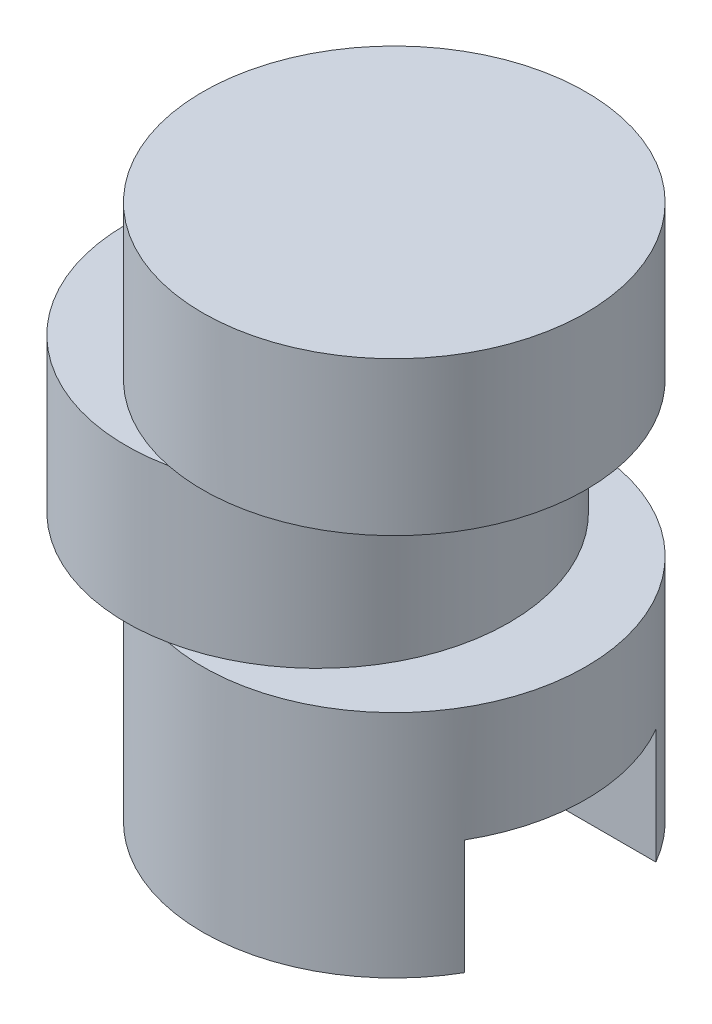
SolidWorks part; units mm, degrees
ref_plane "前视基准面" through (0, 0, 0) normal (0, 0, 1) x (1, 0, 0)
ref_plane "上视基准面" through (0, 0, 0) normal (0, 1, 0) x (1, 0, 0)
ref_plane "右视基准面" through (0, 0, 0) normal (1, 0, 0) x (0, 0, -1)
sketch "草图1" plane through (0, 0, 0) normal (0, 1, 0) x (1, 0, 0)
  circle A0 centre (0, 0) radius 5
  circle A1 centre (-2, 0) radius 5
  point P5 (0, 0)
  dimension "D2" = 10
  dimension "D1" = 2
extrude "凸台-拉伸1" add sketch "草图1" along normal blind 6 contours A1 A0 | A0 A1 region at (3.0885, 0, 3.7827) region at (-1, 0, 0)
extrude "凸台-拉伸2" add sketch "草图1<3>" along normal blind 4 from surface contours A0 A1 | A0 A1 region at (-1, 0, 0) region at (-5.1166, 0, 0) starting at face at (0, 6, 5)
sketch "草图1<3>" plane through (0, 0, 0) normal (0, 1, 0) x (1, 0, 0) same geometry as "草图1"
extrude "凸台-拉伸3" add sketch "草图1<4>" along normal blind 4 from surface contours A0 A1 | A1 A0 region at (3.0885, 0, 3.7827) region at (-1, 0, 0) starting at face at (-2, 10, 5)
sketch "草图1<4>" plane through (0, 0, 0) normal (0, 1, 0) x (1, 0, 0) same geometry as "草图1"
sketch "草图2" plane through (0, 0, 0) normal (0, -1, 0) x (1, 0, 0)
  line L0 (-4.3301, 2.5) -> (4.3301, 2.5)
  line L1 (-5, 0) -> (5, 0) construction
  line L2 (-4.3301, -2.5) -> (4.3301, -2.5)
  arc A0 (-1, 4.899) -> (-1, -4.899) centre (0, 0) ccw construction
  circle A1 centre (0, 0) radius 5 construction
  arc A2 (-4.3301, 2.5) -> (-4.3301, -2.5) centre (0, 0) ccw
  arc A3 (4.3301, -2.5) -> (4.3301, 2.5) centre (0, 0) ccw
  dimension "D1" = 5
extrude "切除-拉伸1" cut sketch "草图2" against normal blind 3
